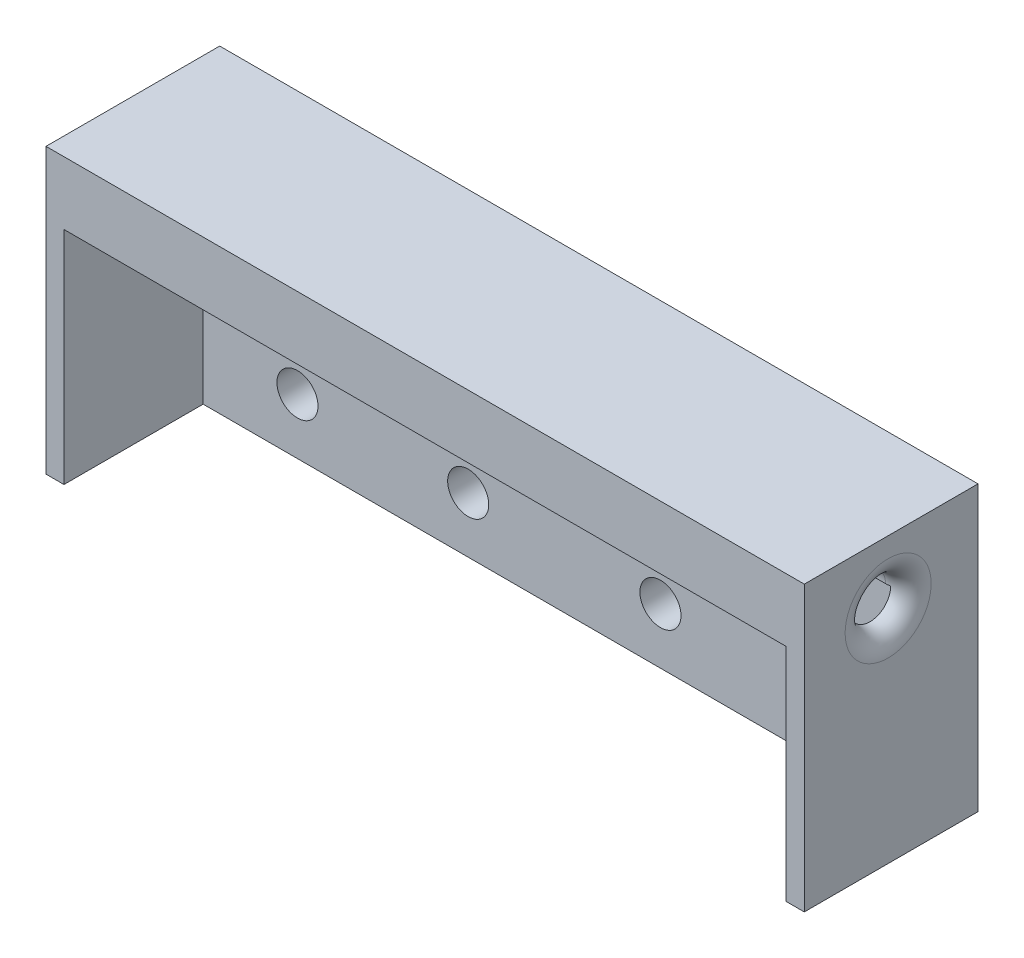
SolidWorks part; units mm, degrees
ref_plane "Front Plane" through (0, 0, 0) normal (0, 0, 1) x (1, 0, 0)
ref_plane "Top Plane" through (0, 0, 0) normal (0, 1, 0) x (1, 0, 0)
ref_plane "Right Plane" through (0, 0, 0) normal (1, 0, 0) x (0, 0, -1)
sketch "Sketch1" plane through (0, 0, 0) normal (0, 0, 1) x (1, 0, 0)
  line L1 (0, 0) -> (42.2, 0)
  line L2 (0, 0) -> (0, 15.8)
  line L3 (0, 15.8) -> (42.2, 15.8)
  line L4 (42.2, 0) -> (42.2, 15.8)
  dimension "D1" = 42.2
  dimension "D2" = 15.8
extrude "Boss-Extrude1" add sketch "Sketch1" along normal blind 9.6667
sketch "Sketch2" plane through (42.2, 0, 0) normal (1, 0, 0) x (0, 0, -1)
  line L0 (0, 0) -> (0, 15.8) construction
  line L1 (-9.6667, 15.8) -> (0, 15.8) construction
  circle A0 centre (-5, 12.3) radius 1.125
  dimension "D2" = 2.25
  dimension "D1" = 5
  dimension "D3" = 3.5
extrude "Cut-Extrude1" cut sketch "Sketch2" against normal through all both and the other way through all
sketch "Sketch3" plane through (0, 0, 9.6667) normal (0, 0, 1) x (1, 0, 0)
  line L0 (0, 0) -> (42.2, 0) construction
  line L1 (1, 0) -> (41.1894, 0)
  line L2 (1, 0) -> (1, 12.2936)
  line L3 (1, 12.2936) -> (41.1894, 12.2936)
  line L4 (41.1894, 0) -> (41.1894, 12.2936)
  line L7 (0, 15.8) -> (0, 0) construction
  dimension "D1" = 12.2936
  dimension "D2" = 40.1894
  dimension "D3" = 1
extrude "Cut-Extrude3" cut sketch "Sketch3" against normal blind 7.7456 contours L2 L1 L4 L3
fillet "Fillet1" radius 1.27 2 edges at (0, 12.3, 3.875) (42.2, 12.3, 6.125)
sketch "Sketch4" plane through (0, 0, 1.9211) normal (0, 0, 1) x (1, 0, 0)
  line L0 (0, 3.1) -> (42.2, 3.1) construction
  line L1 (0, 15.8) -> (0, 0) construction
  line L2 (42.2, 0) -> (42.2, 15.8) construction
  line L3 (1, 0) -> (41.1894, 0) construction
  circle A0 centre (6.25, 3.1) radius 1.143
  circle A1 centre (15.75, 3.1) radius 1.143
  circle A2 centre (26.45, 3.1) radius 1.143
  circle A3 centre (35.95, 3.1) radius 1.143
  point P16 (0, 0)
  dimension "D6" = 2.286
  dimension "D1" = 3.1
  dimension "D2" = 6.25
  dimension "D3" = 9.5
  dimension "D4" = 9.5
  dimension "D5" = 10.7
extrude "Cut-Extrude4" cut sketch "Sketch4" against normal through all both and the other way through all
